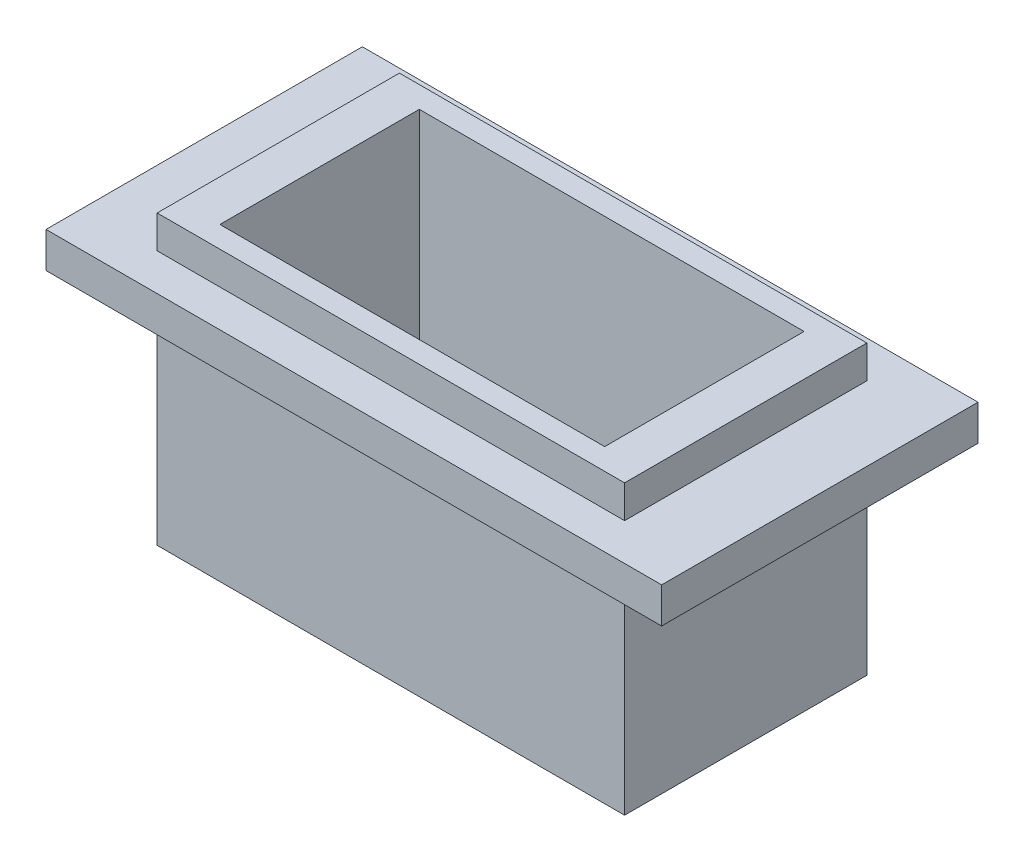
SolidWorks part; units mm, degrees
ref_plane "Front Plane" through (0, 0, 0) normal (0, 0, 1) x (1, 0, 0)
ref_plane "Top Plane" through (0, 0, 0) normal (0, 1, 0) x (1, 0, 0)
ref_plane "Right Plane" through (0, 0, 0) normal (1, 0, 0) x (0, 0, -1)
sketch "Sketch1" plane through (0, 0, 0) normal (0, 1, 0) x (1, 0, 0)
  line L0 (27.432, 28.194) -> (27.432, 0) construction
  line L1 (0, 0) -> (54.864, 0)
  line L2 (0, 0) -> (0, 28.194)
  line L3 (0, 28.194) -> (54.864, 28.194)
  line L4 (54.864, 0) -> (54.864, 28.194)
  line L6 (48.26, 3.302) -> (6.604, 3.302)
  line L7 (48.26, 3.302) -> (48.26, 24.892)
  line L8 (48.26, 24.892) -> (6.604, 24.892)
  line L9 (6.604, 3.302) -> (6.604, 24.892)
  line L10 (48.26, 3.302) -> (6.604, 24.892) construction
  line L11 (48.26, 24.892) -> (6.604, 3.302) construction
  line L12 (10.287, 5.2109) -> (44.577, 5.2109)
  line L13 (10.287, 5.2109) -> (10.287, 22.9831)
  line L14 (10.287, 22.9831) -> (44.577, 22.9831)
  line L15 (44.577, 5.2109) -> (44.577, 22.9831)
  line L16 (10.287, 5.2109) -> (44.577, 22.9831) construction
  line L17 (10.287, 22.9831) -> (44.577, 5.2109) construction
  point P7 (27.432, 14.097)
  point P12 (27.432, 14.097)
  dimension "D1" = 54.864
  dimension "D2" = 28.194
  dimension "D3" = 21.59
  dimension "D4" = 41.656
  dimension "D5" = 34.29
extrude "Boss-Extrude1" add sketch "Sketch1" along normal blind 3.175 contours L1 L4 L3 L2 L6 L9 L8 L7 region at (0.6168, 0, -14.097)
extrude "Boss-Extrude2" add sketch "Sketch1<3>" along normal blind 6.096 and the other way blind 19.558 contours L9 L6 L7 L8 L15 L12 L13 L14 region at (27.432, 0, -3.7712)
sketch "Sketch1<3>" plane through (0, 0, 0) normal (0, 1, 0) x (1, 0, 0) same geometry as "Sketch1"
